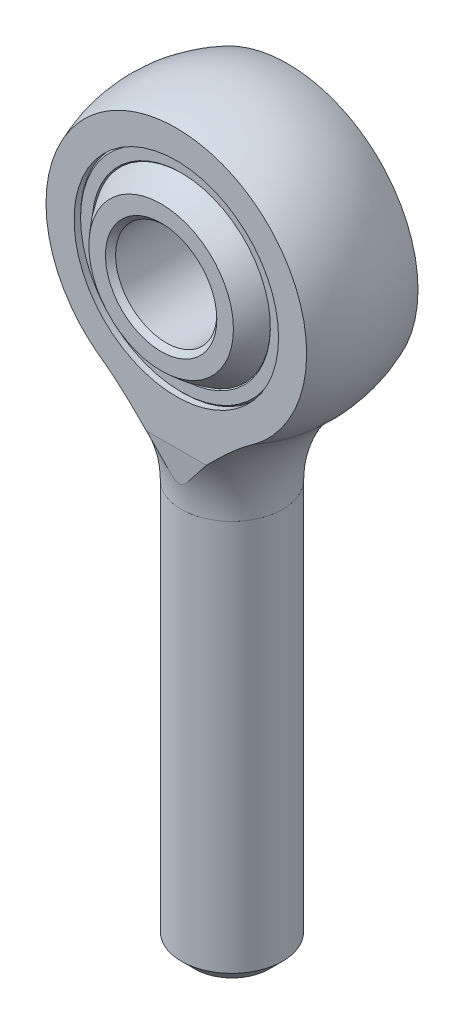
SolidWorks part; units mm, degrees
ref_plane "Front" through (0, 0, 0) normal (0, 0, 1) x (1, 0, 0)
ref_plane "Top" through (0, 0, 0) normal (0, 1, 0) x (1, 0, 0)
ref_plane "Right" through (0, 0, 0) normal (1, 0, 0) x (0, 0, -1)
sketch "Sketch1" plane through (0, 0, 0) normal (0, 0, 1) x (1, 0, 0)
  line L0 (0, 0) -> (0, -31.75)
  line L1 (0, -31.75) -> (3.9688, -31.75)
  line L2 (3.9688, -31.75) -> (3.9688, 0)
  line L3 (3.9688, 0) -> (0, 0)
  line L5 (0, 26.9875) -> (0, 0) construction
  line L6 (0, 26.9875) -> (11.1125, 26.9875) construction
  line L7 (11.1125, 26.9875) -> (11.1125, 15.875) construction
  line L8 (-3.9687, -31.75) -> (-3.9687, 0) construction
  arc A0 (7.3698, 7.558) -> (0, 26.9875) centre (0, 15.875) ccw construction
  circle A1 centre (0, 15.875) radius 3.9688 construction
  circle A2 centre (0, 15.875) radius 7.9375 construction
  circle A3 centre (0, 15.875) radius 8.0169 construction
  arc A4 (3.9688, 0) -> (7.3698, 7.558) centre (14.067, 0) cw construction
  point P16 (-3.9687, -24.6062)
  dimension "A" = 7.9375
  dimension "Ball Dia" = 15.875
  dimension "B" = 22.225
  dimension "D1" = 16.0337
  dimension "D" = 47.625
  dimension "E" = 31.75
  dimension "Thread Dia" = 7.9375
  dimension "D2" = 7.1438
revolve "Revolve1" add sketch "Sketch1" angle 360 about L5
sketch "Sketch12" [suppressed] plane through (0, -31.75, 0) normal (0, -1, 0) x (1, 0, 0)
  circle A1 centre (0, 0) radius 3.9688
  circle A2 centre (0, 0) radius 3.9688
  dimension "D1" = 0
chamfer "Chamfer2" distance 1.0583 angle 45 1 edges at (-3.9687, -31.75, 0)
sketch "Sketch4" plane through (0, 0, 0) normal (0, 0, 1) x (1, 0, 0)
  line L0 (3.9688, 0) -> (0, 0) construction
  line L2 (0, 26.9875) -> (0, 0) construction
  line L3 (3.9688, 0) -> (0, 0)
  line L5 (0, 26.9875) -> (0, 0)
  line L6 (0, 26.9875) -> (0, 29.5275) construction
  arc A0 (7.3698, 7.558) -> (0, 26.9875) centre (0, 15.875) ccw construction
  arc A1 (7.3698, 7.558) -> (0, 26.9875) centre (0, 15.875) ccw
  arc A2 (7.3698, 7.558) -> (3.9688, 0) centre (14.067, 0) ccw construction
  arc A3 (7.3698, 7.558) -> (3.9688, 0) centre (14.067, 0) ccw
  dimension "D1" = 2.54
revolve "Revolve2" add sketch "Sketch4" angle 360 about L6
sketch "Sketch5" plane through (0, 0, 0) normal (1, 0, 0) x (0, 0, -1)
  line L0 (4.3656, 26.9875) -> (11.1125, 26.9875)
  line L1 (-4.3656, 26.9875) -> (4.3656, 26.9875) construction
  line L2 (-4.3656, 26.9875) -> (-4.3656, 4.3656)
  line L3 (-3.9688, 0) -> (3.9688, 0) construction
  line L4 (4.3656, 26.9875) -> (4.3656, 4.3656)
  line L5 (11.1125, 26.9875) -> (11.1125, 0)
  line L6 (11.1125, 0) -> (3.9688, 0)
  line L7 (-3.9688, 0) -> (-11.1125, 0)
  line L8 (-11.1125, 0) -> (-11.1125, 26.9875)
  line L9 (-11.1125, 26.9875) -> (-4.3656, 26.9875)
  line L10 (3.9688, 0) -> (4.3656, 4.3656)
  line L11 (-3.9688, 0) -> (-4.3656, 4.3656)
  line L12 (-4.3656, 4.3656) -> (4.3656, 4.3656) construction
  line L13 (0, 0) -> (0, 4.3656) construction
  arc A0 (7.3698, 7.558) -> (-7.3698, 7.558) centre (0, 15.875) ccw construction
  dimension "F" = 8.7312
  dimension "D2" = 4.3656
  dimension "D1" = 7.9375
extrude "Cut-Extrude1" cut sketch "Sketch5" against normal through all and the other way through all
sketch "Sketch6" plane through (0, 0, 0) normal (0, 0, 1) x (1, 0, 0)
  circle A0 centre (0, 15.875) radius 8.0169 construction
  circle A1 centre (0, 15.875) radius 8.0169
extrude "Cut-Extrude2" cut sketch "Sketch6" against normal through all and the other way through all
sketch "Sketch7" plane through (0, 0, 0) normal (0, 0, 1) x (1, 0, 0)
  line L0 (0, 23.8125) -> (0, 7.9375)
  line L1 (0, 26.9875) -> (0, 0) construction
  line L2 (0, 0) -> (0, 7.9375) construction
  arc A0 (0, 7.9375) -> (0, 23.8125) centre (0, 15.875) ccw
  circle A1 centre (0, 15.875) radius 7.9375 construction
revolve "Revolve3" add sketch "Sketch7" angle 360 about L2
sketch "Sketch8" plane through (0, 0, 0) normal (1, 0, 0) x (0, 0, -1)
  line L0 (-4.3656, 26.9875) -> (4.3656, 26.9875) construction
  line L1 (-5.5562, 26.9875) -> (5.5562, 26.9875) construction
  line L2 (-5.5562, 26.9875) -> (-5.5563, 0)
  line L3 (-5.5563, 0) -> (5.5563, 0) construction
  line L4 (5.5562, 26.9875) -> (5.5563, 0)
  line L5 (5.5562, 26.9875) -> (11.1125, 26.9875)
  line L6 (11.1125, 26.9875) -> (11.1125, 0)
  line L7 (11.1125, 0) -> (5.5563, 0)
  line L8 (-5.5563, 0) -> (-11.1125, 0)
  line L9 (-11.1125, 0) -> (-11.1125, 26.9875)
  line L10 (-11.1125, 26.9875) -> (-5.5562, 26.9875)
  dimension "C" = 11.1125
extrude "Cut-Extrude3" cut sketch "Sketch8" against normal through all and the other way through all
sketch "Sketch10" plane through (0, 0, 0) normal (0, 0, 1) x (1, 0, 0)
  circle A0 centre (0, 15.875) radius 3.9688 construction
  circle A1 centre (0, 15.875) radius 3.9688
extrude "Cut-Extrude4" cut sketch "Sketch10" against normal through all and the other way through all
chamfer "Chamfer1" distance 0.3969 angle 45 2 edges at (3.9687, 15.875, -5.5562) (3.9687, 15.875, 5.5562)
sketch "Sketch14" plane through (0, 0, 0) normal (1, 0, 0) x (0, 0, -1)
  line L0 (-3.9846, 23.8919) -> (-3.9846, 22.7399)
  line L1 (-3.9846, 23.8919) -> (-1.6558, 23.8919)
  line L2 (-1.6558, 23.8919) -> (-1.6558, 23.6379)
  line L3 (3.9846, 22.7399) -> (3.9846, 23.8919)
  line L4 (3.9846, 23.8919) -> (1.6558, 23.8919)
  line L5 (1.6558, 23.8919) -> (1.6558, 23.6379)
  line L8 (-5.5562, 15.875) -> (5.5562, 15.875) construction
  line L9 (-5.5562, 21.5435) -> (-5.5562, 10.2065) construction
  line L10 (4.3656, 23.8919) -> (-4.3656, 23.8919) construction
  line L11 (-4.3656, 26.094) -> (-4.3656, 7.558) construction
  arc A1 (3.9846, 22.7399) -> (1.6558, 23.6379) centre (0, 15.875) ccw
  arc A2 (-1.6558, 23.6379) -> (-3.9846, 22.7399) centre (0, 15.875) ccw
  arc A3 (5.5562, 21.5435) -> (-5.5562, 21.5435) centre (0, 15.875) ccw construction
  dimension "D1" = 0.381
  dimension "D2" = 0.254
revolve "Revolve4" add sketch "Sketch14" angle 360 about L8
chamfer "Chamfer3" distance 0.127 angle 45 2 edges at (0, 7.8581, 3.9846) (0, 9.0101, 3.9846) first distance on face at (0, 7.8581, 3.9846) first distance on face at (0, 9.0101, 3.9846)
chamfer "Chamfer4" distance 0.127 angle 45 2 edges at (0, 9.0101, -3.9846) (0, 7.8581, -3.9846) first distance on face at (0, 9.0101, -3.9846) first distance on face at (0, 7.8581, -3.9846)
sketch "Sketch11" plane through (0, 0, 0) normal (1, 0, 0) x (0, 0, -1)
  line L0 (0, 15.875) -> (-5.5563, 16.5572) construction
  line L1 (4.3656, 15.875) -> (-4.3656, 15.875) construction
  line L2 (0, 15.875) -> (-5.5563, 15.1928) construction
  line L3 (0, 26.9875) -> (0, 0) construction
  line L4 (-5.5562, 26.9875) -> (-5.5563, 0) construction
  line L5 (0, 15.875) -> (0.0074, 15.875) construction
  dimension "Swivel" = 14
curve "Helix/Spiral1" [suppressed] pitch 1.0583 height 33.1248 turns 31.299 parameters "pitch"=1.0583
sketch "Sketch13" [suppressed] plane through (0, 0, 0) normal (1, 0, 0) x (0, 0, -1)
  line L0 (-3.9688, -32.676) -> (-3.9688, -31.75)
  line L1 (-3.9688, -31.75) -> (-3.2813, -32.1469)
  line L2 (-3.2813, -32.1469) -> (-3.2813, -32.2792)
  line L3 (-3.2813, -32.2792) -> (-3.9688, -32.676)
  line L4 (-3.2813, -32.213) -> (-3.9688, -32.213) construction
  line L5 (-3.625, -32.4776) -> (-3.625, -31.9484) construction
  line L6 (-3.9688, -31.75) -> (3.9688, -31.75) construction
  dimension "D1" = 0.1323
  dimension "D2" = 0.5292
  dimension "D3" = 60
sweep "Cut-Sweep1" [suppressed] cut profiles "Sketch13" path "Helix/Spiral1"
sketch "Sketch15" [suppressed] plane through (0, 0, 0) normal (0, -1, 0) x (1, 0, 0)
  arc A2 (0, -3.9688) -> (0, 3.9688) centre (0, 0) ccw
  arc A3 (0, 3.9688) -> (0, -3.9688) centre (0, 0) ccw
  arc A5 (0, 3.9688) -> (0, -3.9688) centre (0, 0) ccw
  arc A6 (0, -3.9688) -> (0, 3.9688) centre (0, 0) ccw
  dimension "D1" = 0
extrude "Boss-Extrude1" [suppressed] add sketch "Sketch15" along normal up to next draft 20
ref_axis "Center Axis 1" through (0, 15.875, -1.6345) along (0, 0, 1)
ref_axis "Center Axis 2" through (0, 29.9353, 0) along (0, -1, 0)
ref_axis "Axis1" through (0, 0, 0) along (0, -1, 0)
ref_point "Point2"
equation "\"D1@Sketch1\"=\"Ball Dia@Sketch1\"*1.01"
equation "\"D1@Chamfer1\"=\"A@Sketch1\"/20"
equation "\"D1@Sketch5\"=\"Thread Dia@Sketch1\""
equation "\"D2@Sketch5\"=\"F@Sketch5\"/2"
equation "\"D1@Sketch13\" = \"pitch@Helix/Spiral1\"*.125"
equation "\"D2@Sketch13\" = \"pitch@Helix/Spiral1\"*.50"
equation "\"D1@Chamfer2\" = \"pitch@Helix/Spiral1\""
equation "\"D2@Sketch1\" = \"pitch@Helix/Spiral1\"*6.750"
equation "\"D3@Helix/Spiral1\"=\"E@Sketch1\"+\"pitch@Helix/Spiral1\"+.0124578"
